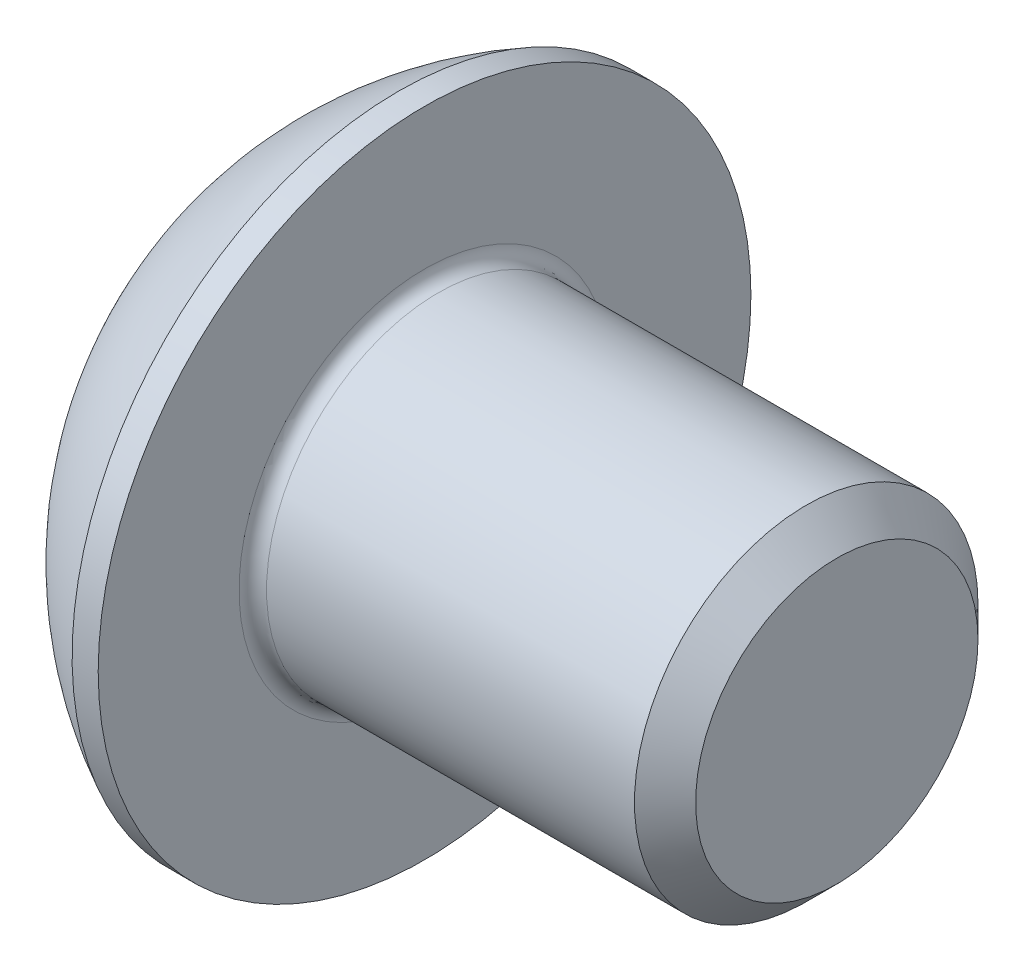
SolidWorks part; units mm, degrees
material "AISI 1020 Steel, Cold Rolled"
ref_plane "Спереди" through (0, 0, 0) normal (0, 0, 1) x (1, 0, 0)
ref_plane "Сверху" through (0, 0, 0) normal (0, 1, 0) x (1, 0, 0)
ref_plane "Справа" through (0, 0, 0) normal (1, 0, 0) x (0, 0, -1)
sketch "Эскиз1" plane through (0, 0, 0) normal (0, 0, 1) x (1, 0, 0)
  line L0 (-3.6435, 0) -> (-10.508, 0) construction
  line L1 (0, 2.375) -> (0, 0)
  line L2 (0, 0) -> (8.75, 0)
  line L3 (8.75, 0) -> (8.75, 2.055)
  line L4 (8.75, 2.055) -> (8.305, 2.5)
  line L5 (8.305, 2.5) -> (2.75, 2.5)
  line L6 (2.75, 2.5) -> (2.75, 4.75)
  line L7 (2.75, 4.75) -> (2.3702, 4.75)
  arc A0 (2.3702, 4.75) -> (0, 2.375) centre (4.7549, 0) ccw
  dimension "D1" = 10.63
  dimension "D2" = 4.75
  dimension "D3" = 2.75
  dimension "D4" = 5
  dimension "D5" = 45
  dimension "D6" = 4.11
  dimension "D7" = 6
  dimension "D8" = 9.5
revolve "Body" add sketch "Эскиз1" angle 360 about L0
fillet "Скругление1" radius 0.2 1 edges at (2.75, 0, -2.5)
sketch "Эскиз2" plane through (0, 0, 0) normal (0, 0, 1) x (1, 0, 0)
  line L0 (0, 0) -> (0, 1.5)
  line L1 (0, 2.375) -> (0, -2.375) construction
  line L2 (0, 1.5) -> (1.56, 1.5)
  line L3 (1.56, 1.5) -> (2.426, 0)
  line L4 (2.426, 0) -> (0, 0)
  dimension "D1" = 1.56
  dimension "D2" = 60
  dimension "D3" = 1.5
revolve "Вырез-Повернуть1" cut sketch "Эскиз2" angle 360 about L4
sketch "Эскиз3" plane through (0, 0, 0) normal (-1, 0, 0) x (0, 0, 1)
  line L1 (-1.5, -0.866) -> (0, -1.7321)
  line L2 (0, -1.7321) -> (1.5, -0.866)
  line L3 (1.5, -0.866) -> (1.5, 0.866)
  line L4 (1.5, 0.866) -> (0, 1.7321)
  line L5 (0, 1.7321) -> (-1.5, 0.866)
  line L6 (-1.5, 0.866) -> (-1.5, -0.866)
  circle A0 centre (0, 0) radius 1.5 construction
  dimension "D1" = 3
extrude "Hex" cut sketch "Эскиз3" against normal blind 1.56
